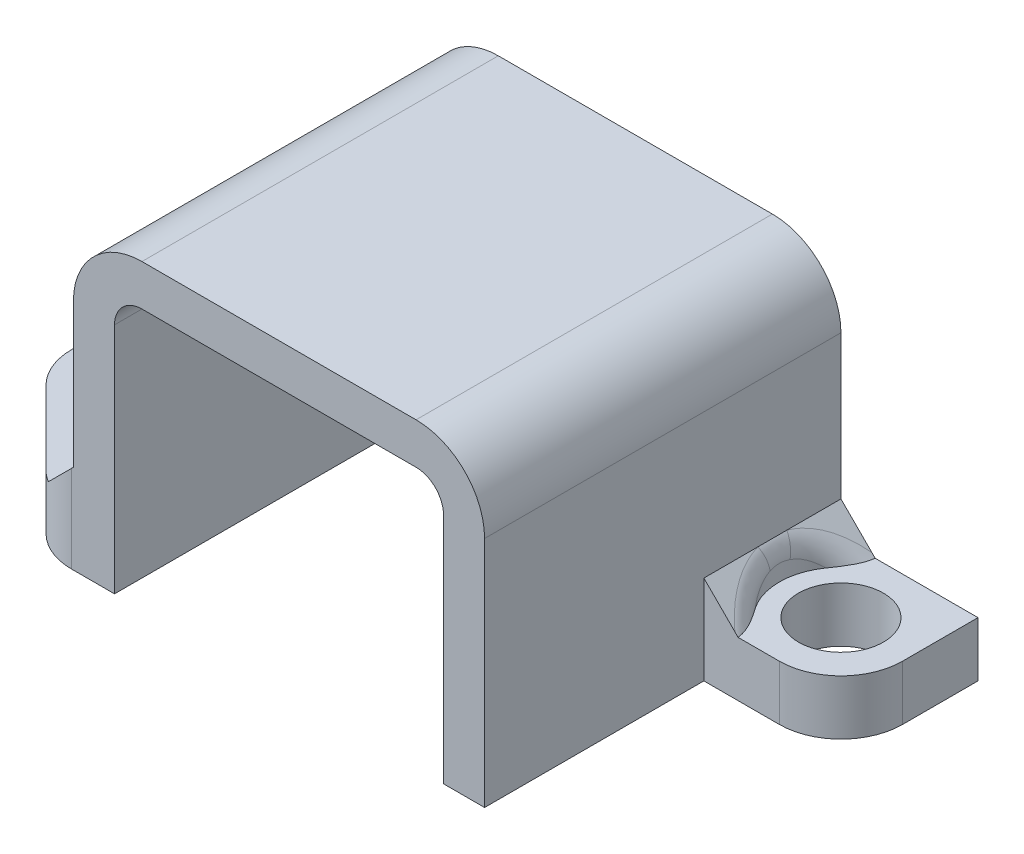
SolidWorks part; units mm, degrees
ref_plane "Front Plane" through (0, 0, 0) normal (0, 0, 1) x (1, 0, 0)
ref_plane "Top Plane" through (0, 0, 0) normal (0, 1, 0) x (1, 0, 0)
ref_plane "Right Plane" through (0, 0, 0) normal (1, 0, 0) x (0, 0, -1)
sketch "Sketch1" plane through (0, 0, 0) normal (0, 0, 1) x (1, 0, 0)
  line L0 (0, 1.5) -> (0, -9.7234) construction
  line L1 (6, 0) -> (-6, 0)
  line L2 (-6, 0) -> (-6, -9.5)
  line L3 (-6, -9.5) -> (-12.5, -9.5)
  line L4 (-12.5, -9.5) -> (-12.5, -7.5)
  line L5 (-12.5, -7.5) -> (-7.5, -7.5)
  line L6 (-7.5, -7.5) -> (-7.5, 1.5)
  line L7 (-7.5, 1.5) -> (7.5, 1.5)
  line L8 (12.5, -9.5) -> (12.5, -7.5)
  line L9 (12.5, -7.5) -> (7.5, -7.5)
  line L10 (6, -9.5) -> (12.5, -9.5)
  line L11 (6, 0) -> (6, -9.5)
  line L12 (7.5, -7.5) -> (7.5, 1.5)
  point P9 (-9.25, -9.5)
  point P17 (0, 0)
  dimension "D1" = 9.5
  dimension "D2" = 12
  dimension "D3" = 1.5
  dimension "D4" = 1.5
  dimension "D5" = 5
  dimension "D6" = 2
extrude "Boss-Extrude1" add sketch "Sketch1" along normal blind 13
sketch "Sketch2" plane through (0, -7.5, 0) normal (0, 1, 0) x (1, 0, 0)
  line L0 (7.5, -13) -> (7.5, 0) construction
  line L1 (12.5, -13) -> (7.5, -13)
  line L2 (12.5, -13) -> (12.5, -5)
  line L3 (12.5, -5) -> (7.5, -5)
  line L4 (7.5, -13) -> (7.5, -5)
  line L5 (12.5, 0) -> (7.5, 0) construction
  dimension "D1" = 5
extrude "Cut-Extrude1" cut sketch "Sketch2" against normal through all
sketch "Sketch3" plane through (0, -7.5, 0) normal (0, 1, 0) x (1, 0, 0)
  line L0 (12.5, -2.5) -> (-12.5, -2.5) construction
  line L1 (12.5, -5) -> (12.5, 0) construction
  line L2 (-12.5, -13) -> (-12.5, 0) construction
  circle A0 centre (10, -2.5) radius 1.55
  circle A1 centre (-10, -2.5) radius 1.55
  dimension "D1" = 3.1
  dimension "D2" = 2.5
  dimension "D3" = 3.1
  dimension "D4" = 2.5
extrude "Cut-Extrude2" cut sketch "Sketch3" against normal through all
fillet "Fillet1" radius 1 2 edges at (-6, 0, 6.5) (6, 0, 6.5)
fillet "Fillet2" radius 2.5 2 edges at (-7.5, 1.5, 6.5) (7.5, 1.5, 6.5)
chamfer "Chamfer1" distance 4 angle 45 1 edges at (-12.5, -8.5, 13)
fillet "Fillet3" radius 2.25 2 edges at (-12.5, -8.5, 9) (-8.5, -8.5, 13)
fillet "Fillet4" radius 2.25 1 edges at (12.5, -8.5, 5)
chamfer "Chamfer2" distance 1.25 angle 45 2 edges at (-7.5, -7.5, 6.5) (7.5, -7.5, 2.5)
sketch "Sketch4" plane through (0, -7.5, 0) normal (0, 1, 0) x (1, 0, 0)
  circle A0 centre (-10, -2.5) radius 2.25
  circle A1 centre (10, -2.5) radius 2.25
  dimension "D1" = 4.5
  dimension "D2" = 4.5
extrude "Cut-Extrude3" cut sketch "Sketch4" along normal blind 5
fillet "Fillet5" radius 1 2 edges at (-7.75, -6.5, 2.5) (7.75, -6.5, 2.5)
